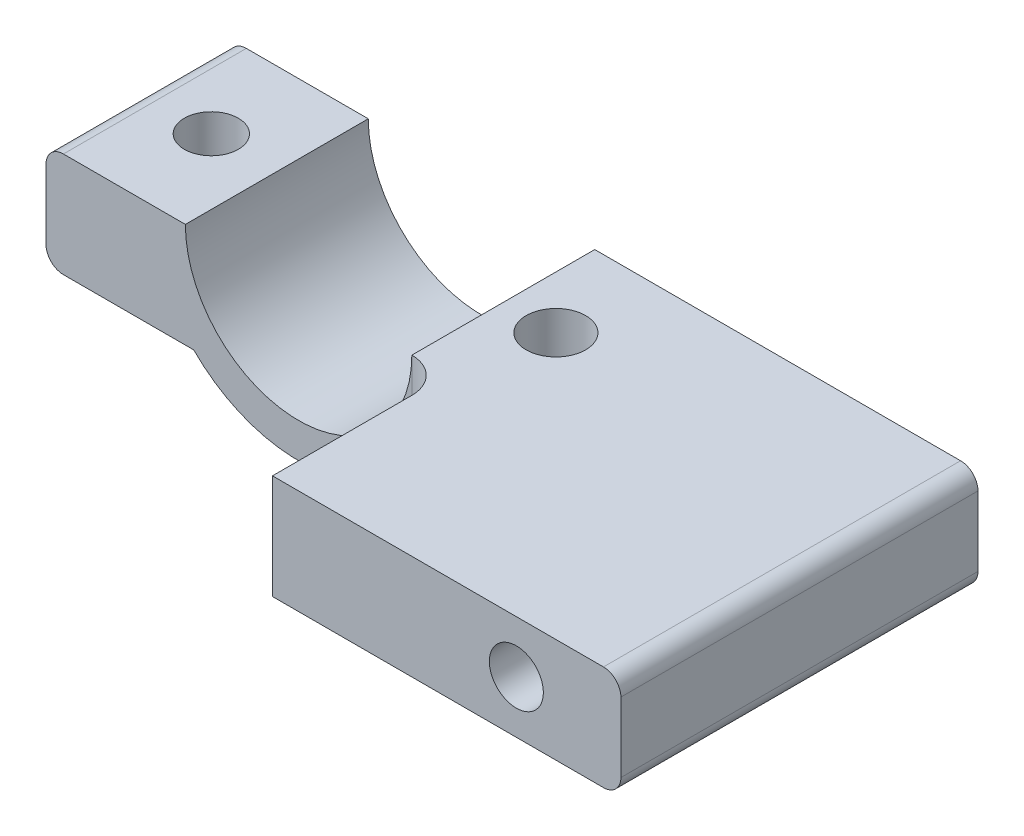
SolidWorks part; units mm, degrees
ref_plane "前视基准面" through (0, 0, 0) normal (0, 0, 1) x (1, 0, 0)
ref_plane "上视基准面" through (0, 0, 0) normal (0, 1, 0) x (1, 0, 0)
ref_plane "右视基准面" through (0, 0, 0) normal (1, 0, 0) x (0, 0, -1)
other "Configuration Table"
sketch "草图1" plane through (0, 0, 0) normal (0, 0, 1) x (1, 0, 0)
  line L1 (-8.5, 0) -> (-6.5, 0)
  line L2 (-8.5, 0) -> (-14.5, 0)
  line L3 (-14.5, 0) -> (-14.5, -6)
  line L4 (-14.5, -6) -> (-6.0208, -6)
  line L5 (8.5, 0) -> (28.5, 0)
  line L6 (28.5, 0) -> (28.5, -6)
  line L7 (28.5, -6) -> (6.0208, -6)
  line L8 (6.5, 0) -> (8.5, 0)
  arc A0 (-6.5, 0) -> (6.5, 0) centre (0, 0) ccw
  arc A1 (-8.5, 0) -> (8.5, 0) centre (0, 0) ccw
  dimension "D1" = 13
  dimension "D2" = 17
  dimension "D3" = 6
  dimension "D4" = 6
  dimension "D5" = 20
  dimension "D6" = 6
extrude "凸台-拉伸1" add sketch "草图1" along normal blind 10.5 contours A1 L2 L3 L4 | L1 A1 L8 A0 | A1 L7 L6 L5 region at (-11.0762, -3.1762, 0) region at (-7.5, -0.1901, 0) region at (18.1019, -3.0575, 0)
sketch "草图2" plane through (0, -6, 0) normal (0, -1, 0) x (1, 0, 0)
  line L0 (-6.0208, 10.5) -> (-14.5, 0) construction
  circle A0 centre (-10.2604, 5.25) radius 1.55
  dimension "D1" = 3.1
extrude "切除-拉伸1" cut sketch "草图2" against normal through all
sketch "草图3" plane through (0, -6, 0) normal (0, -1, 0) x (1, 0, 0)
  line L0 (6.0208, 5.25) -> (9.5208, 5.25) construction
  line L1 (6.0208, 10.5) -> (6.0208, 0) construction
  circle A0 centre (9.5208, 5.25) radius 1.7073
  dimension "D1" = 3.5
extrude "切除-拉伸2" cut sketch "草图3" against normal through all
sketch "草图5" plane through (0, 0, 10.5) normal (0, 0, 1) x (1, 0, 0)
  line L0 (6.5, 0) -> (28.5, 0) construction
  line L1 (28.5, -6) -> (8.5, -6)
  line L2 (28.5, -6) -> (28.5, 0)
  line L3 (28.5, 0) -> (8.5, 0)
  line L4 (8.5, -6) -> (8.5, 0)
  dimension "D1" = 20
extrude "凸台-拉伸2" add sketch "草图5" along normal blind 10
sketch "草图6" plane through (0, 0, 20.5) normal (0, 0, 1) x (1, 0, 0)
  circle A0 centre (22.5, -3) radius 1.55
extrude "切除-拉伸4" cut sketch "草图6" against normal blind 10
fillet "圆角1" radius 2 1 edges at (8.5, -3, 10.5)
fillet "圆角2" radius 1 4 edges at (28.5, 0, 10.25) (28.5, -6, 10.25) (-14.5, -6, 5.25) (-14.5, 0, 5.25)
